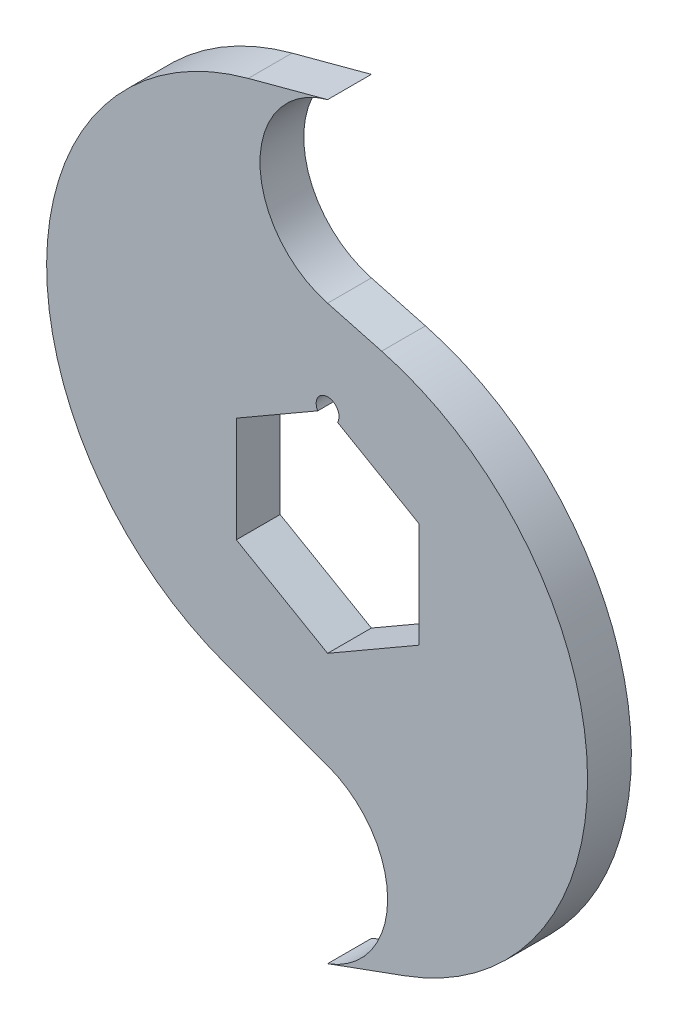
SolidWorks part; units mm, degrees
ref_plane "Front Plane" through (0, 0, 0) normal (0, 0, 1) x (1, 0, 0)
ref_plane "Top Plane" through (0, 0, 0) normal (0, 1, 0) x (1, 0, 0)
ref_plane "Right Plane" through (0, 0, 0) normal (1, 0, 0) x (0, 0, -1)
sketch "Sketch1" plane through (0, 0, 0) normal (0, 0, 1) x (1, 0, 0)
  line L0 (0, 52.07) -> (-11.0405, 49.1117)
  line L1 (0, 52.07) -> (0, 0) construction
  line L2 (0, -52.07) -> (10.7407, -48.1607)
  line L3 (0, 0) -> (0, -52.07) construction
  line L5 (0, 14.6647) -> (-12.7, 7.3323)
  line L6 (-12.7, 7.3323) -> (-12.7, -7.3323)
  line L7 (-12.7, -7.3323) -> (0, -14.6647)
  line L8 (0, -14.6647) -> (12.7, -7.3323)
  line L9 (12.7, -7.3323) -> (12.7, 7.3323)
  line L10 (12.7, 7.3323) -> (0, 14.6647)
  line L11 (0, 27.5355) -> (7.5237, 25.5195)
  line L12 (0, -28.2018) -> (-14.1906, -23.0368)
  circle A0 centre (0, 0) radius 52.07 construction
  arc A1 (0, 52.07) -> (0, 27.5355) centre (3.287, 39.8027) ccw
  arc A3 (0, -52.07) -> (0, -28.2018) centre (-4.3437, -40.1359) ccw
  arc A4 (10.7407, -48.1607) -> (7.5237, 25.5195) centre (-2.4834, -11.8278) ccw
  arc A5 (-11.0405, 49.1117) -> (-14.1906, -23.0368) centre (-1.2414, 12.5408) ccw
  circle A6 centre (0, 0) radius 12.7 construction
  circle A7 centre (0, 14.6647) radius 1.5875
  dimension "D4" = 70
  dimension "D5" = 25.4
  dimension "D1" = 104.14
  dimension "D6" = 12.7
  dimension "D7" = 3.175
  dimension "D2" = 11.43
  dimension "D3" = 75
extrude "Boss-Extrude1" add sketch "Sketch1" along normal mid plane 6.096 contours L0 A5 L12 A3 L2 A4 L11 A1 A7 L10 L9 L8 L7 L6 L5 region at (-10.698, 39.8027, 0)
